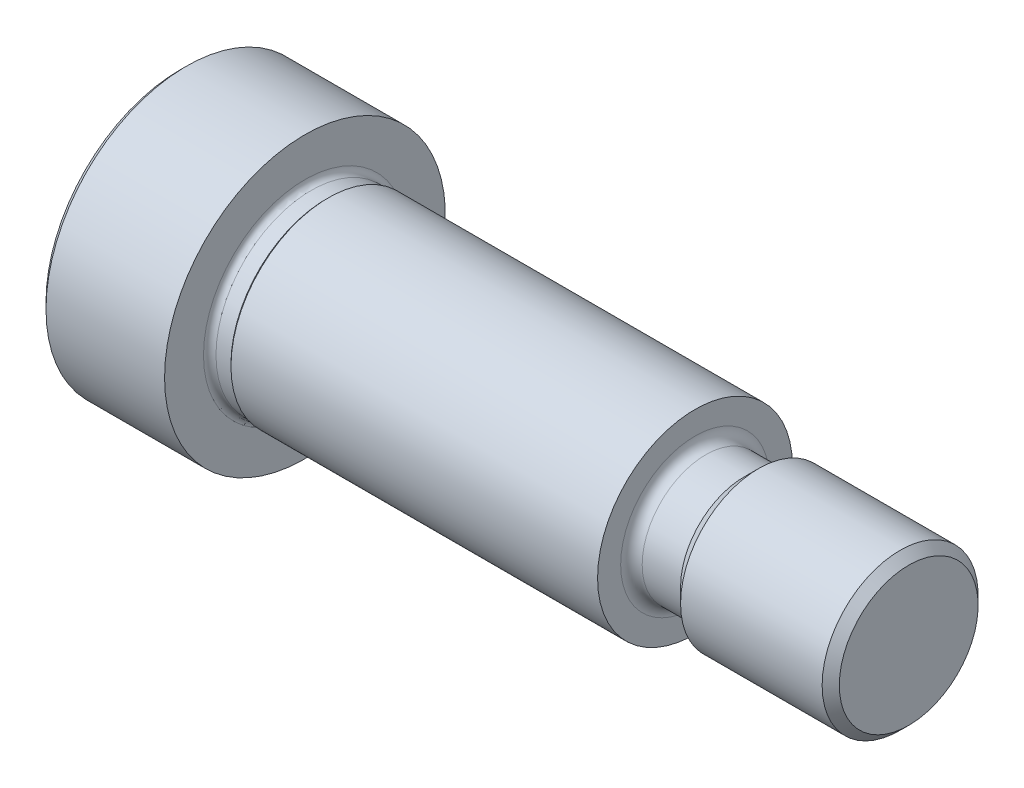
SolidWorks part; units mm, degrees
ref_plane "Plane1" through (0, 0, 0) normal (0, 0, 1) x (1, 0, 0)
ref_plane "Plane2" through (0, 0, 0) normal (0, 1, 0) x (1, 0, 0)
ref_plane "Plane3" through (0, 0, 0) normal (1, 0, 0) x (0, 0, -1)
sketch "BodySke" plane through (0, 0, 0) normal (0, 0, 1) x (1, 0, 0)
  line L0 (0, 0) -> (0, 18)
  line L2 (0, 18) -> (16, 18)
  line L3 (16, 18) -> (16, 13.01)
  line L4 (16.8, 12.21) -> (18.72, 12.21)
  line L5 (18.72, 12.21) -> (19, 12.49)
  line L6 (19, 12.49) -> (66, 12.49)
  line L7 (66, 12.49) -> (66, 9.53)
  line L8 (67.38, 8.15) -> (72.3, 8.15)
  line L9 (72.3, 8.15) -> (74.15, 10)
  line L10 (74.15, 10) -> (92.2985, 10)
  line L11 (92.2985, 10) -> (93.4, 8.8985)
  line L12 (93.4, 8.8985) -> (93.4, 0)
  line L13 (93.4, 0) -> (0, 0)
  line L14 (-6.35, 0) -> (107.95, 0) construction
  line L15 (92.2985, -10) -> (93.4, -8.8985) construction
  line L16 (66, -8.15) -> (72.3, -8.15) construction
  line L17 (19, -12.49) -> (66, -12.49) construction
  line L18 (16, -12.21) -> (18.72, -12.21) construction
  line L20 (74.8, 13.0014) -> (74.8, -4.3514) construction
  line L21 (70.54, 12.6746) -> (70.54, -3.175) construction
  arc A0 (66, 9.53) -> (67.38, 8.15) centre (67.38, 9.53) ccw
  arc A1 (16.8, 12.21) -> (16, 13.01) centre (16.8, 13.01) cw
  point P29 (66, 8.15)
  point P32 (16, 12.21)
  dimension "D11" = 45
  dimension "D13" = 45
  dimension "Advance" = 2.5
  dimension "Head_dia" = 36
  dimension "Diameter" = 24.98
revolve "BaseBody" add sketch "BodySke" angle 360 about L14
cosmetic thread "ThreadCosmetic" [suppressed] parameters "Thread_length"=18.6, "Thread_minor"=17.797
chamfer "Chamfer1" distance 0.8 angle 45 1 edges at (0, 0, 18)
sketch "Sketch2" plane through (0, 0, 0) normal (0, 0, 1) x (1, 0, 0)
  line L0 (0, 6) -> (10, 6)
  line L1 (10, 6) -> (13.4641, 0)
  line L3 (13.4641, 0) -> (0, 0)
  line L4 (0, 0) -> (0, 6)
  line L5 (0, -6) -> (10, -6) construction
  line L6 (0, 0) -> (47.625, 0) construction
  dimension "D2" = 60
  dimension "PreBroach_depth" = 10
  dimension "PreBroach_dia" = 12
revolve "PreBroach" cut sketch "Sketch2" angle 360 about L6
sketch "Sketch3" plane through (0, 0, 0) normal (-1, 0, 0) x (0, 0, 1)
  line L0 (-6, -3.4641) -> (-6, 3.4641)
  line L1 (-6, 3.4641) -> (0, 6.9282)
  line L2 (0, 6.9282) -> (6, 3.4641)
  line L3 (6, 3.4641) -> (6, -3.4641)
  line L4 (6, -3.4641) -> (0, -6.9282)
  line L5 (0, -6.9282) -> (-6, -3.4641)
  dimension "Hex_size" = 12
  dimension "D1" = 6
  dimension "D2" = 6
  dimension "D3" = 120
  dimension "D4" = 12
extrude "Hex" cut sketch "Sketch3" against normal blind 10
sketch "ThdSchSke" plane through (0, 0, 0) normal (0, 0, 1) x (1, 0, 0)
  line L0 (74.8, -8.8985) -> (72.2852, -12.49)
  line L1 (74.8, -8.8985) -> (77.3148, -12.49)
  line L2 (77.3148, -12.49) -> (77.3148, -15.6125)
  line L3 (-3.175, 0) -> (5.1513, 0) construction
  line L5 (77.3148, -15.6125) -> (72.2852, -15.6125)
  line L6 (72.2852, -15.6125) -> (72.2852, -12.49)
  dimension "Thread_minor" = 17.797
  dimension "Diameter" = 24.98
  dimension "Start" = 74.8
revolve "ThreadSchematic" [suppressed] cut sketch "ThdSchSke" angle 360 about L3
pattern_linear "ThdSchPat" [suppressed]
equation "\"Thread_minor@ThreadCosmetic\" = \"Minor_dia@BodySke\""
equation "\"D1@Sketch3\" = \"Hex_size@Sketch3\" / 2"
equation "\"D2@Sketch3\" = \"D1@Sketch3\""
equation "\"D4@Sketch3\" = \"Hex_size@Sketch3\""
equation "\"Width@Chamfer1\" = \"Head_fillet_radius@BodySke\""
equation "\"Thread_length@ThreadCosmetic\" = ((sgn( (\"Thread_length@BodySke\" - \"Advance@BodySke\" - \"Thread_neck_width@BodySke\" ) - \"Thread_nom@BodySke\" )-1)*( (\"Thread_length@BodySke\" - \"Advance@BodySke\" - \"Thread_neck_width@BodySke\" ) - \"Thread_nom@BodySke\" ))/-2+ \"Thread_nom@BodySke\""
equation "\"Thread_minor@ThdSchSke\" = \"Minor_dia@BodySke\""
equation "\"Diameter@ThdSchSke\" = \"Diameter@BodySke\""
equation "\"Overcut@ThdSchSke\" = \"Diameter@BodySke\" * 1.25"
equation "\"Start@ThdSchSke\" = \"Head_ht@BodySke\" + \"Length@BodySke\" + \"Thread_length@BodySke\" -  \"Thread_length@ThreadCosmetic\"  '---Non-countersunk---"
equation "\"Num_threads@ThdSchPat\" = int( \"Thread_length@ThreadCosmetic\" / \"Advance@BodySke\" + 0.999 ) + 1"
equation "\"Advance@ThdSchPat\" = \"Thread_length@ThreadCosmetic\" /  (\"Num_threads@ThdSchPat\" - 1) 'relax it"
equation "\"Num_threads@ThdSchPat\" = \"Num_threads@ThdSchPat\" - sgn( \"Num_threads@ThdSchPat\" - 1) '---chamfered tips only---"
